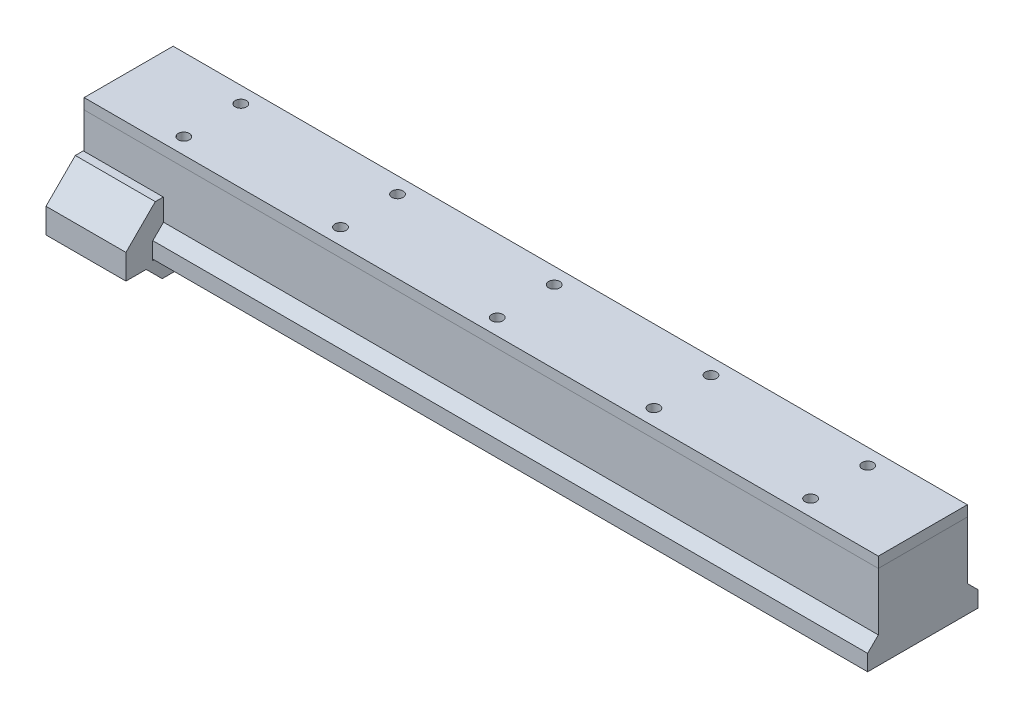
SolidWorks part; units mm, degrees
ref_plane "Front Plane" through (0, 0, 0) normal (0, 0, 1) x (1, 0, 0)
ref_plane "Top Plane" through (0, 0, 0) normal (0, 1, 0) x (1, 0, 0)
ref_plane "Right Plane" through (0, 0, 0) normal (1, 0, 0) x (0, 0, -1)
sketch "Sketch1" plane through (0, 0, 0) normal (0, 1, 0) x (1, 0, 0)
  line L0 (-2.35, -2.35) -> (2.35, -2.35)
  line L1 (-2.35, -2.35) -> (-2.35, 2.35)
  line L2 (-2.35, 2.35) -> (2.35, 2.35)
  line L3 (2.35, 2.35) -> (2.35, -2.35)
  line L4 (17.05, 2.35) -> (17.05, -2.35)
  line L5 (12.35, -2.35) -> (17.05, -2.35)
  line L6 (12.35, -2.35) -> (12.35, 2.35)
  line L7 (12.35, 2.35) -> (17.05, 2.35)
  line L8 (31.75, 2.35) -> (31.75, -2.35)
  line L9 (27.05, -2.35) -> (31.75, -2.35)
  line L10 (27.05, -2.35) -> (27.05, 2.35)
  line L11 (27.05, 2.35) -> (31.75, 2.35)
  line L12 (46.45, 2.35) -> (46.45, -2.35)
  line L13 (41.75, -2.35) -> (46.45, -2.35)
  line L14 (41.75, -2.35) -> (41.75, 2.35)
  line L15 (41.75, 2.35) -> (46.45, 2.35)
  line L16 (61.15, 2.35) -> (61.15, -2.35)
  line L17 (56.45, -2.35) -> (61.15, -2.35)
  line L18 (56.45, -2.35) -> (56.45, 2.35)
  line L19 (56.45, 2.35) -> (61.15, 2.35)
  line L20 (75.85, 2.35) -> (75.85, -2.35)
  line L21 (71.15, -2.35) -> (75.85, -2.35)
  line L22 (71.15, -2.35) -> (71.15, 2.35)
  line L23 (71.15, 2.35) -> (75.85, 2.35)
  line L24 (90.55, 2.35) -> (90.55, -2.35)
  line L25 (85.85, -2.35) -> (90.55, -2.35)
  line L26 (85.85, -2.35) -> (85.85, 2.35)
  line L27 (85.85, 2.35) -> (90.55, 2.35)
  line L28 (105.25, 2.35) -> (105.25, -2.35)
  line L29 (100.55, -2.35) -> (105.25, -2.35)
  line L30 (100.55, -2.35) -> (100.55, 2.35)
  line L31 (100.55, 2.35) -> (105.25, 2.35)
  line L32 (119.95, 2.35) -> (119.95, -2.35)
  line L33 (115.25, -2.35) -> (119.95, -2.35)
  line L34 (115.25, -2.35) -> (115.25, 2.35)
  line L35 (115.25, 2.35) -> (119.95, 2.35)
  line L36 (134.65, 2.35) -> (134.65, -2.35)
  line L37 (129.95, -2.35) -> (134.65, -2.35)
  line L38 (129.95, -2.35) -> (129.95, 2.35)
  line L39 (129.95, 2.35) -> (134.65, 2.35)
  line L40 (-2.35, 2.35) -> (2.35, -2.35) construction
  line L41 (-8.35, 8.35) -> (140.65, 8.35)
  line L42 (-8.35, 8.35) -> (-8.35, -8.35)
  line L43 (-8.35, -8.35) -> (140.65, -8.35)
  line L44 (140.65, 8.35) -> (140.65, -8.35)
  dimension "D1" = 4.7
  dimension "D2" = 4.7
  dimension "D4" = 10
  dimension "D5" = 6
  dimension "D6" = 6
  dimension "D7" = 6
  dimension "D8" = 6
  dimension "D3" = 10
extrude "Boss-Extrude1" add sketch "Sketch1" along normal blind 15
extrude "Boss-Extrude2" add sketch "Sketch1<2>" against normal blind 0.8 contours L43 L44 L41 L42
sketch "Sketch1<2>" plane through (0, 0, 0) normal (0, 1, 0) x (1, 0, 0) same geometry as "Sketch1"
sketch "Sketch3" plane through (-8.35, 0, 0) normal (-1, 0, 0) x (0, 0, 1)
  line L0 (-8.35, -0.8) -> (-10.35, -0.8)
  line L1 (-8.35, 4.2) -> (-10.35, 2.2)
  line L3 (-8.35, 15) -> (-8.35, -0.8) construction
  line L4 (-10.35, 2.2) -> (-10.35, -0.8)
  line L5 (0, 0) -> (0, 5.4486) construction
  line L6 (-8.35, 4.2) -> (-8.35, -0.8)
  line L7 (-8.5, 4.2621) -> (-10.5, 2.2621)
  line L8 (-10.5, 2.2621) -> (-10.5, -0.95)
  line L9 (-10.5, -0.95) -> (10.5, -0.95)
  line L10 (-8.5, 4.2621) -> (-8.5, 8.419)
  line L11 (-8.5, 8.419) -> (-10, 8.419)
  line L12 (-10, 8.419) -> (-15.5, 2.919)
  line L13 (-15.5, 2.919) -> (-15.5, -1.75)
  line L14 (-15.5, -1.75) -> (15.5, -1.75)
  line L15 (10.5, 2.2621) -> (10.5, -0.95)
  line L16 (15.5, 2.919) -> (15.5, -1.75)
  line L17 (10, 8.419) -> (15.5, 2.919)
  line L18 (8.5, 8.419) -> (10, 8.419)
  line L19 (8.35, 4.2) -> (10.35, 2.2)
  line L20 (10.35, 2.2) -> (10.35, -0.8)
  line L21 (8.35, -0.8) -> (10.35, -0.8)
  line L22 (8.35, 4.2) -> (8.35, -0.8)
  line L23 (8.5, 4.2621) -> (10.5, 2.2621)
  line L24 (8.5, 8.419) -> (8.5, 4.2621)
  point P21 (0, -0.95)
  point P22 (0, -1.75)
  line M6 (-8.35, 15) -> (-8.35, -0.8)
  line M8 (8.35, -0.8) -> (8.35, 15)
  dimension "D1" = 135
  dimension "D2" = 2
  dimension "D3" = 3
  dimension "D4" = 0.15
  dimension "D5" = 0.15
  dimension "D6" = 0.15
  dimension "D7" = 4
  dimension "D8" = 5
  dimension "D9" = 0.8
  dimension "D10" = 1.5
  dimension "D11" = 0.15
extrude "Boss-Extrude3" add sketch "Sketch3" against normal up to surface (149 mm away) contours L1 L4 L0 M6 | L21 L20 L19 M8 region at (-8.35, 1.2417, -9.2667) region at (-8.35, 1.2417, 9.2667) up to face at (140.65, 7.1, 0)
extrude "Boss-Extrude4" add sketch "Sketch3<3>" against normal blind 15 separate body contours L23 L15 L9 L8 L7 L11 L12 L13 L14 L16 L17 L18 M8 M6 region at (-8.35, 3.4928, -9.7307)
sketch "Sketch3<3>" plane through (-8.35, 0, 0) normal (-1, 0, 0) x (0, 0, 1) same geometry as "Sketch3"
sketch "Sketch4" plane through (0, -1.75, 0) normal (0, -1, 0) x (1, 0, 0)
  line L0 (-3.025, 1.7) -> (1.325, -1.7) construction
  line L1 (-3.025, 1.7) -> (1.325, 1.7)
  line L2 (-3.025, 1.7) -> (-3.025, -1.7)
  line L3 (-3.025, -1.7) -> (1.325, -1.7)
  line L4 (1.325, 1.7) -> (1.325, -1.7)
  line L5 (-2.45, 1.7) -> (-2.45, 15.5)
  line L6 (0.75, 1.7) -> (0.75, 15.5)
  line L7 (-2.45, 15.5) -> (0.75, 1.7) construction
  line L8 (6.65, 15.5) -> (-8.35, 15.5) construction
  line L9 (-2.45, 15.5) -> (-8.35, 15.5)
  line L10 (-8.35, 15.5) -> (-8.35, -15.5)
  line L11 (6.65, -15.5) -> (-8.35, -15.5) construction
  line L12 (-8.35, -15.5) -> (-8.35, 15.5) construction
  line L13 (-8.35, -15.5) -> (6.65, -15.5)
  line L14 (6.65, -15.5) -> (6.65, 15.5)
  line L15 (6.65, 15.5) -> (0.75, 15.5)
  line L16 (-8.35, -15.5) -> (6.65, 15.5) construction
  line L17 (-8.35, 7.7) -> (6.65, 7.7)
  point P9 (-0.85, 8.6)
  point P10 (-0.85, 1.7)
  point P24 (-0.85, 0)
  line M6 (-8.35, 15.5) -> (-8.35, -15.5)
  line M7 (-8.35, -15.5) -> (6.65, -15.5)
  line M8 (6.65, -15.5) -> (6.65, 15.5)
  line M9 (6.65, 15.5) -> (-8.35, 15.5)
  dimension "D1" = 4.35
  dimension "D2" = 3.4
  dimension "D3" = 3.2
  dimension "D4" = 6
extrude "Boss-Extrude5" add sketch "Sketch4" along normal blind 3 contours L6 L1 L4 L3 L2 L5 M9 M6 M7 M8 region at (-0.85, -1.75, -4.6095)
sketch "Sketch5" plane through (0, 15, 0) normal (0, 1, 0) x (1, 0, 0)
  line L0 (140.65, -8.35) -> (140.65, 8.35) construction
  line L1 (-8.35, 8.35) -> (140.65, 8.35)
  line L2 (-8.35, 8.35) -> (-8.35, -8.35)
  line L3 (-8.35, -8.35) -> (140.65, -8.35)
  line L4 (140.65, 8.35) -> (140.65, -8.35)
  line L5 (-8.35, -8.35) -> (140.65, -8.35) construction
  line L6 (0, 2.35) -> (0, 8.35) construction
  line L7 (0, -2.35) -> (0, -8.35) construction
  line L8 (2.35, 2.35) -> (-2.35, 2.35) construction
  line L9 (-2.35, -2.35) -> (2.35, -2.35) construction
  line L10 (0, 5.35) -> (7.35, 5.35) construction
  line L11 (7.35, -5.35) -> (0, -5.35) construction
  line L12 (2.35, 0) -> (12.35, 0) construction
  line L13 (2.35, -2.35) -> (2.35, 2.35) construction
  line L14 (12.35, 2.35) -> (12.35, -2.35) construction
  line L15 (7.35, 5.35) -> (7.35, 0) construction
  line L16 (31.75, 0) -> (41.75, 0) construction
  line L17 (31.75, -2.35) -> (31.75, 2.35) construction
  line L18 (41.75, 2.35) -> (41.75, -2.35) construction
  line L19 (36.75, 0) -> (36.75, 5.35) construction
  circle A0 centre (7.35, 5.35) radius 1.05
  circle A1 centre (7.35, -5.35) radius 1.05
  circle A2 centre (36.75, 5.35) radius 1.05
  circle A3 centre (36.75, -5.35) radius 1.05
  circle A4 centre (66.15, 5.35) radius 1.05
  circle A5 centre (66.15, -5.35) radius 1.05
  circle A6 centre (95.55, 5.35) radius 1.05
  circle A7 centre (95.55, -5.35) radius 1.05
  circle A8 centre (124.95, 5.35) radius 1.05
  circle A9 centre (124.95, -5.35) radius 1.05
  dimension "D1" = 2.1
  dimension "D2" = 5
extrude "Boss-Extrude6" add sketch "Sketch5" along normal blind 2 separate body
extrude "Cut-Extrude1" cut sketch "Sketch5<2>" against normal blind 10 contours A0 | A1 | A2 | A3 | A5 | A4 | A6 | A7 | A8 | A9
sketch "Sketch5<2>" plane through (0, 15, 0) normal (0, 1, 0) x (1, 0, 0) same geometry as "Sketch5"
sketch "Sketch7" plane through (0, -4.75, 0) normal (0, -1, 0) x (1, 0, 0)
  line L0 (-5.85, 2.5) -> (4.15, 2.5)
  line L1 (-5.85, -2.5) -> (4.15, -2.5)
  line L2 (-0.85, 2.5) -> (-0.85, -2.5) construction
  line L3 (-5.85, 0) -> (4.15, 0) construction
  line L4 (-8.35, 7.7) -> (-8.35, -15.5) construction
  line L5 (6.65, -15.5) -> (6.65, 7.7) construction
  circle A0 centre (-5.85, 0) radius 1.5
  circle A1 centre (4.15, 0) radius 1.5
  circle A2 centre (-5.85, 0) radius 1.6
  circle A3 centre (4.15, 0) radius 1.6
  circle A4 centre (-5.85, 0) radius 2.5
  circle A5 centre (4.15, 0) radius 2.5
  point P6 (-0.85, 0)
  line M7 (0.75, 7.7) -> (0.75, 1.7)
  line M8 (0.75, 1.7) -> (1.325, 1.7)
  line M9 (1.325, 1.7) -> (1.325, -1.7)
  line M10 (1.325, -1.7) -> (-3.025, -1.7)
  line M11 (-3.025, -1.7) -> (-3.025, 1.7)
  line M12 (-3.025, 1.7) -> (-2.45, 1.7)
  line M13 (-2.45, 1.7) -> (-2.45, 7.7)
  dimension "D1" = 3
  dimension "D2" = 0.1
  dimension "D3" = 1
  dimension "D4" = 1
extrude "Cut-Extrude2" cut sketch "Sketch7" against normal blind 3.2 contours A2 | A3
extrude "Boss-Extrude8" add sketch "Sketch7<4>" against normal blind 3 separate body contours A0 | A1 region at (-5.85, -4.75, 0) region at (4.15, -4.75, 0)
sketch "Sketch7<4>" plane through (0, -4.75, 0) normal (0, -1, 0) x (1, 0, 0) same geometry as "Sketch7"
extrude "Boss-Extrude9" add sketch "Sketch7<5>" along normal blind 1.5 contours A4 A2 | L0 M13 M12 M11 M10 M9 M8 M7 | A5 L0 A4 L1 M7 M8 M9 M10 M11 M12 M13 | A5 A3 | A3 A1 | A2 A0 | A0 | A1 region at (-4.15, -4.75, 2.3882) region at (-4.1322, -4.75, 1.7178) region at (-0.85, -4.75, 0.3099) region at (1.7207, -4.75, 0) region at (-5.85, -4.75, 0) region at (4.15, -4.75, 0) region at (-7.4047, -4.75, 0) region at (2.5953, -4.75, 0)
sketch "Sketch7<5>" plane through (0, -4.75, 0) normal (0, -1, 0) x (1, 0, 0) same geometry as "Sketch7"
sketch "Sketch8" plane through (0, -4.75, 0) normal (0, 1, 0) x (1, 0, 0)
  line L8 (0.75, -1.7) -> (1.325, -1.7)
  line L9 (0.75, -7.7) -> (0.75, -1.7)
  line L10 (-8.35, -15.5) -> (6.65, -15.5)
  line L11 (-2.45, -1.7) -> (-2.45, -7.7)
  line L12 (-3.025, -1.7) -> (-2.45, -1.7)
  line L13 (-3.025, 1.7) -> (-3.025, -1.7)
  line L14 (1.325, 1.7) -> (-3.025, 1.7)
  line L15 (1.325, -1.7) -> (1.325, 1.7)
  line L16 (0.75, -1.7) -> (1.325, -1.7)
  line L20 (-3.025, -1.7) -> (-2.45, -1.7)
  line L21 (-3.025, 1.7) -> (-3.025, -1.7)
  line L22 (1.325, 1.7) -> (-3.025, 1.7)
  line L23 (1.325, -1.7) -> (1.325, 1.7)
  line L24 (0.75, -1.55) -> (1.175, -1.55)
  line L25 (1.175, -1.55) -> (1.175, 1.55)
  line L26 (1.175, 1.55) -> (-2.875, 1.55)
  line L27 (-2.875, 1.55) -> (-2.875, -1.55)
  line L29 (-2.875, -1.55) -> (-2.45, -1.55)
  line L30 (-2.45, -1.55) -> (0.75, -1.55)
  line L41 (-8.35, -7.7) -> (-8.35, -15.5)
  line L43 (-2.45, -7.7) -> (-8.35, -7.7)
  line L45 (6.65, -7.7) -> (0.75, -7.7)
  line L47 (6.65, -15.5) -> (6.65, -7.7)
  dimension "D1" = 0
  dimension "D2" = 0.15
extrude "Boss-Extrude10" add sketch "Sketch8" along normal blind 1.5 contours L29 L30 L24 L25 L26 L27 region at (-0.85, -4.75, 0)
chamfer "Chamfer1" distance 4 angle 45 2 edges at (3.7, -1.75, 7.7) (-5.4, -1.75, 7.7)
